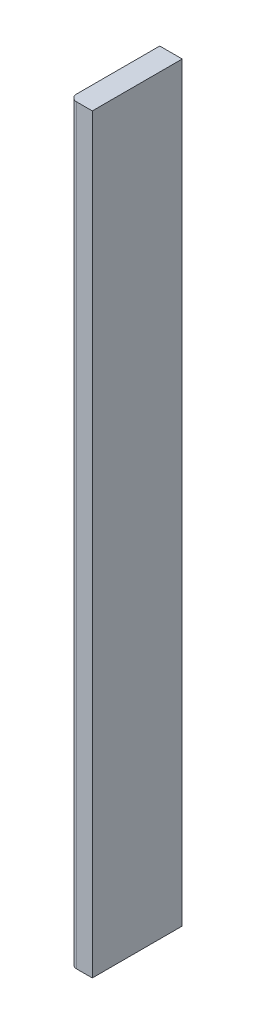
SolidWorks part; units mm, degrees
ref_plane "Спереди" through (0, 0, 0) normal (0, 0, 1) x (1, 0, 0)
ref_plane "Сверху" through (0, 0, 0) normal (0, 1, 0) x (1, 0, 0)
ref_plane "Справа" through (0, 0, 0) normal (1, 0, 0) x (0, 0, -1)
sketch "Эскиз1" plane through (-0.1, 0, 0) normal (-1, 0, 0) x (0, 0, 1)
  line L0 (4, -16.7) -> (0, -16.7)
  line L1 (0, -16.9) -> (0, 16.9) construction
  line L2 (-6, -16.7) -> (4, -16.7) construction
  line L3 (0, -16.7) -> (0, 16.7)
  line L4 (4, 16.7) -> (-6, 16.7) construction
  line L5 (0, 16.7) -> (4, 16.7)
  line L6 (4, 16.7) -> (4, -16.7)
  point P7 (0, -16.7)
extrude "Бобышка-Вытянуть1" add sketch "Эскиз1" along normal blind 1
fillet "Скругление1" radius 0.3 1 edges at (-1.1, 0, 4)
